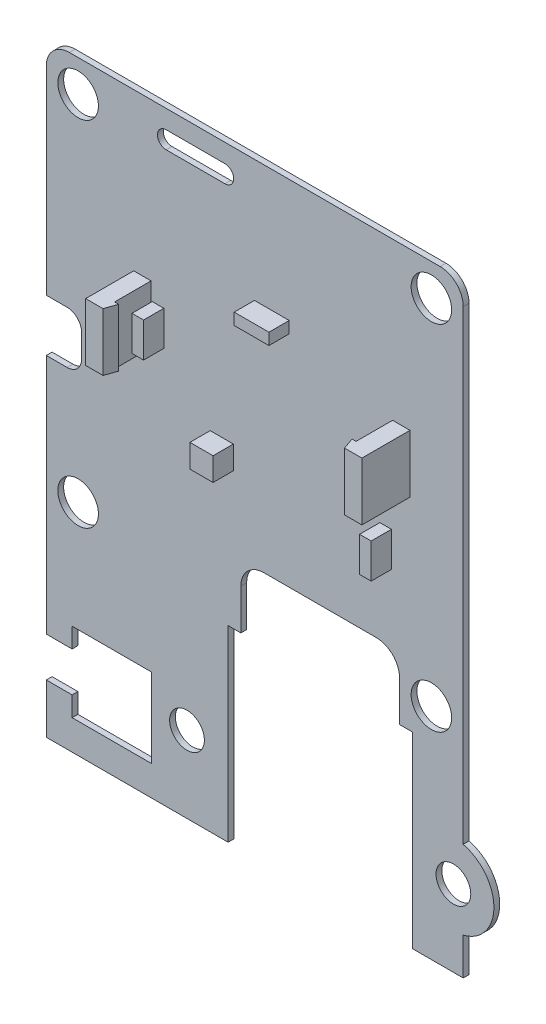
SolidWorks part; units mm, degrees
ref_plane "Front Plane" through (0, 0, 0) normal (0, 0, 1) x (1, 0, 0)
ref_plane "Top Plane" through (0, 0, 0) normal (0, 1, 0) x (1, 0, 0)
ref_plane "Right Plane" through (0, 0, 0) normal (1, 0, 0) x (0, 0, -1)
sketch "Sketch1" plane through (0, 0, 0) normal (0, 0, 1) x (1, 0, 0)
  line L1 (-14.95, -2.4) -> (-14.95, -4.4) construction
  line L2 (-16.2, -1.15) -> (-16.2, -5.65)
  line L3 (-14.95, -2.4) -> (-14.95, -4.4)
  line L4 (-7.65, 14.9) -> (-2.57, 14.9) construction
  line L5 (13.6, -18.1) -> (13.6, -34.2)
  line L6 (13.6, -34.2) -> (18, -34.2)
  line L7 (-2.3, -34.2) -> (-2.3, -18.1)
  line L8 (16, 18) -> (-16, 18)
  line L9 (-18, 16) -> (-18, -1.15)
  line L10 (-18, -18) -> (-1.2, -18)
  line L11 (-1.2, -18) -> (-1.2, -14.5)
  line L12 (0.8, -12.5) -> (10.5, -12.5)
  line L13 (12.5, -14.5) -> (12.5, -18)
  line L14 (12.5, -18) -> (18, -18)
  line L15 (18, -18) -> (18, 16)
  line L16 (16, 18) -> (-16, 18)
  line L17 (-18, 16) -> (-18, -1.15)
  line L18 (-18, -18) -> (-1.2, -18)
  line L19 (-1.2, -18) -> (-1.2, -14.5)
  line L20 (0.8, -12.5) -> (10.5, -12.5)
  line L21 (12.5, -14.5) -> (12.5, -18)
  line L22 (12.5, -18) -> (18, -18)
  line L23 (18, -18) -> (18, 16)
  line L24 (-2.3, -18.1) -> (-18, -18.1)
  line L25 (-18, -18.1) -> (-18, -26.4854)
  line L29 (-18, -34.2) -> (-2.3, -34.2)
  line L30 (-2.3, -34.2) -> (-2.3, -18.1)
  line L31 (-2.3, -18.1) -> (-18, -18.1)
  line L32 (-18, -18.1) -> (-18, -26.4854)
  line L36 (-18, -34.2) -> (-2.3, -34.2)
  line L37 (18, -34.2) -> (18, -30.9952)
  line L38 (18, -24.2048) -> (18, -18.1)
  line L39 (18, -18.1) -> (13.6, -18.1)
  line L40 (13.6, -18.1) -> (13.6, -34.2)
  line L41 (13.6, -34.2) -> (18, -34.2)
  line L42 (18, -34.2) -> (18, -30.9952)
  line L43 (18, -24.2048) -> (18, -18.1)
  line L44 (18, -18.1) -> (13.6, -18.1)
  line L45 (-7.65, 16.4) -> (-2.57, 16.4) construction
  line L46 (-7.65, 14.9) -> (-2.57, 14.9)
  line L47 (-7.65, 16.4) -> (-2.57, 16.4)
  line L48 (-18, -1.15) -> (-18, -18.1)
  line L49 (18, -18) -> (18, -18.1)
  line L50 (13.6, -18.1) -> (13.6, -18)
  line L51 (-2.3, -18.1) -> (-2.3, -18)
  line L112 (-18, -1.15) -> (-16.2, -1.15)
  line L113 (-18, -1.15) -> (-16.2, -1.15)
  line L114 (-14.95, -2.4) -> (-14.95, -4.4)
  line L115 (-14.95, -2.4) -> (-14.95, -4.4)
  line L116 (-16.2, -5.65) -> (-18, -5.65)
  line L117 (-16.2, -5.65) -> (-18, -5.65)
  line L118 (-18, -5.65) -> (-18, -18)
  line L119 (-18, -5.65) -> (-18, -18)
  line L153 (-18, -26.4854) -> (-15.77, -26.4854)
  line L154 (-18, -26.4854) -> (-15.77, -26.4854)
  line L155 (-15.77, -26.4854) -> (-15.77, -24.78)
  line L156 (-15.77, -26.4854) -> (-15.77, -24.78)
  line L157 (-15.77, -24.78) -> (-8.93, -24.78)
  line L158 (-15.77, -24.78) -> (-8.93, -24.78)
  line L186 (-15.77, -29.9146) -> (-18, -29.9146)
  line L187 (-15.77, -29.9146) -> (-18, -29.9146)
  line L234 (-8.93, -24.78) -> (-8.93, -31.62)
  line L235 (-8.93, -24.78) -> (-8.93, -31.62)
  line L236 (-8.93, -31.62) -> (-15.77, -31.62)
  line L237 (-8.93, -31.62) -> (-15.77, -31.62)
  line L238 (-15.77, -31.62) -> (-15.77, -29.9146)
  line L239 (-15.77, -31.62) -> (-15.77, -29.9146)
  line L240 (-18, -29.9146) -> (-18, -34.2)
  line L241 (-18, -29.9146) -> (-18, -34.2)
  arc A0 (-16.2, -5.65) -> (-14.95, -4.4) centre (-16.2, -4.4) ccw construction
  arc A3 (18, -30.9952) -> (18, -24.2048) centre (17.15, -27.6) ccw
  arc A4 (-16, 18) -> (-18, 16) centre (-16, 16) ccw
  arc A5 (0.8, -12.5) -> (-1.2, -14.5) centre (0.8, -14.5) ccw
  arc A6 (12.5, -14.5) -> (10.5, -12.5) centre (10.5, -14.5) ccw
  arc A7 (18, 16) -> (16, 18) centre (16, 16) ccw
  arc A8 (-16, 18) -> (-18, 16) centre (-16, 16) ccw
  arc A9 (0.8, -12.5) -> (-1.2, -14.5) centre (0.8, -14.5) ccw
  arc A10 (12.5, -14.5) -> (10.5, -12.5) centre (10.5, -14.5) ccw
  arc A11 (18, 16) -> (16, 18) centre (16, 16) ccw
  arc A12 (18, -30.9952) -> (18, -24.2048) centre (17.15, -27.6) ccw
  arc A13 (-14.95, -2.4) -> (-16.2, -1.15) centre (-16.2, -2.4) ccw construction
  arc A14 (-16.2, -5.65) -> (-14.95, -4.4) centre (-16.2, -4.4) ccw
  arc A15 (-14.95, -2.4) -> (-16.2, -1.15) centre (-16.2, -2.4) ccw
  circle A18 centre (17.15, -27.6) radius 1.5 construction
  circle A19 centre (-5.85, -27.6) radius 1.5 construction
  circle A22 centre (15.25, 15.25) radius 1.75
  circle A23 centre (15.25, -15.25) radius 1.75
  circle A24 centre (17.15, -27.6) radius 1.5
  circle A25 centre (-5.85, -27.6) radius 1.5
  circle A26 centre (-15.25, -15.25) radius 1.75
  circle A27 centre (-15.25, 15.25) radius 1.75
  arc A28 (-2.57, 14.9) -> (-2.57, 16.4) centre (-2.57, 15.65) ccw construction
  arc A29 (-7.65, 16.4) -> (-7.65, 14.9) centre (-7.65, 15.65) ccw construction
  arc A30 (-2.57, 14.9) -> (-2.57, 16.4) centre (-2.57, 15.65) ccw
  arc A31 (-7.65, 16.4) -> (-7.65, 14.9) centre (-7.65, 15.65) ccw
  circle A46 centre (15.25, -15.25) radius 1.75 construction
  circle A47 centre (-15.25, -15.25) radius 1.75 construction
  circle A48 centre (-15.25, 15.25) radius 1.75 construction
  circle A49 centre (15.25, 15.25) radius 1.75 construction
  arc A62 (-14.95, -2.4) -> (-16.2, -1.15) centre (-16.2, -2.4) ccw
  arc A63 (-14.95, -2.4) -> (-16.2, -1.15) centre (-16.2, -2.4) ccw
  arc A64 (-16.2, -5.65) -> (-14.95, -4.4) centre (-16.2, -4.4) ccw
  arc A65 (-16.2, -5.65) -> (-14.95, -4.4) centre (-16.2, -4.4) ccw
  dimension "D1" = 0
  dimension "D2" = 0
  dimension "D3" = 0
extrude "Base shape" add sketch "Sketch1" along normal blind 0.5 contours L23 A11 L16 A8 L17 L18 L19 A9 L20 A10 L21 L22 A31 L47 A30 L46 A27 A26 A23 A22 A15 L3 A14 L2 | L31 L51 L18 L48 | L36 L30 L31 L32 A25 | L50 L44 L49 L22 | L42 A12 L43 L44 L40 L41 A24 region at (-0.1312, 0.8573, 0) region at (-10.15, -18.05, 0) region at (-10.15, -18.3249, 0) region at (15.8, -18.05, 0) region at (16.2483, -26.2681, 0)
sketch "Sketch2" plane through (0, 0, 0.5) normal (0, 0, 1) x (1, 0, 0)
  line L0 (1.475, 16.95) -> (1.475, -13.05) construction
  line L1 (-7.85, 1.45) -> (-8.85, 1.45) construction
  line L2 (-0.025, 7.45) -> (2.975, 7.45)
  line L3 (-0.025, 7.45) -> (-0.025, 6.45)
  line L4 (11.8, 16.95) -> (-8.85, 16.95)
  line L5 (-8.85, 16.95) -> (-8.85, -13.05)
  line L6 (-8.85, -13.05) -> (11.8, -13.05)
  line L7 (11.8, -13.05) -> (11.8, 16.95)
  line L8 (11.8, 16.95) -> (-8.85, 16.95)
  line L9 (-8.85, 16.95) -> (-8.85, -13.05)
  line L10 (-8.85, -13.05) -> (11.8, -13.05)
  line L11 (11.8, -13.05) -> (11.8, 16.95)
  line L12 (-0.025, 6.45) -> (2.975, 6.45)
  line L13 (2.975, 7.45) -> (2.975, 6.45)
  line L14 (-0.025, 7.45) -> (2.975, 6.45) construction
  line L15 (-0.025, 6.45) -> (2.975, 7.45) construction
  line L16 (-8.85, 2.95) -> (-7.85, 2.95)
  line L17 (-8.85, 2.95) -> (-8.85, -0.05)
  line L18 (-8.85, -0.05) -> (-7.85, -0.05)
  line L19 (-7.85, 2.95) -> (-7.85, -0.05)
  line L20 (-3.85, -4.2) -> (-1.85, -4.2)
  line L21 (-3.85, -4.2) -> (-3.85, -6.2)
  line L22 (-3.85, -6.2) -> (-1.85, -6.2)
  line L23 (-1.85, -4.2) -> (-1.85, -6.2)
  line L24 (11.8, -3.75) -> (10.8, -3.75)
  line L25 (11.8, -3.75) -> (11.8, -6.75)
  line L26 (11.8, -6.75) -> (10.8, -6.75)
  line L27 (10.8, -3.75) -> (10.8, -6.75)
  line L28 (11.8, 1.95) -> (10.8, 1.95)
  line L29 (11.8, 1.95) -> (11.8, -1.05)
  line L30 (11.8, -1.05) -> (10.8, -1.05)
  line L31 (10.8, 1.95) -> (10.8, -1.05)
  line L32 (-3.85, -5.2) -> (-1.85, -5.2) construction
  line L33 (-2.85, -4.2) -> (-2.85, -6.2) construction
  line L34 (10.8, 0.45) -> (11.8, 0.45) construction
  line L35 (10.8, -5.25) -> (11.8, -5.25) construction
  point P6 (1.475, 6.95)
  dimension "D2" = 3
  dimension "D3" = 1
  dimension "D4" = 10
  dimension "D5" = 7.8
  dimension "D6" = 16.5
  dimension "D7" = 7.85
  dimension "D8" = 6
  dimension "D9" = 2
  dimension "D10" = 15.5
  dimension "D1" = 0
extrude "RX supports" add sketch "Sketch2" along normal blind 1.75 contours L13 L2 L3 L12 | L19 L16 L9 L18 | L23 L20 L21 L22 | L28 L31 L30 L11 | L24 L27 L26 L11 region at (1.475, 6.95, 0.5) region at (11.3, 0.45, 0.5) region at (-8.35, 1.45, 0.5) region at (11.3, -5.25, 0.5) region at (-2.85, -5.2, 0.5)
sketch "Sketch3" plane through (0, 0, 0.5) normal (0, 0, 1) x (1, 0, 0)
  line L0 (-8.85, 1.95) -> (11.8, 1.95) construction
  line L1 (1.475, 16.95) -> (1.475, -13.05) construction
  line L2 (-8.95, 4.45) -> (-10.45, 4.45)
  line L3 (-8.95, 4.45) -> (-8.95, -0.55)
  line L4 (11.8, 16.95) -> (-8.85, 16.95)
  line L5 (-8.85, 16.95) -> (-8.85, -13.05)
  line L6 (-8.85, -13.05) -> (11.8, -13.05)
  line L7 (11.8, -13.05) -> (11.8, 16.95)
  line L8 (11.8, 16.95) -> (-8.85, 16.95)
  line L9 (-8.85, 16.95) -> (-8.85, -13.05)
  line L10 (-8.85, -13.05) -> (11.8, -13.05)
  line L11 (11.8, -13.05) -> (11.8, 16.95)
  line L12 (-8.95, -0.55) -> (-10.45, -0.55)
  line L13 (-10.45, 4.45) -> (-10.45, -0.55)
  line L14 (11.9, -0.55) -> (13.4, -0.55)
  line L15 (13.4, 4.45) -> (13.4, -0.55)
  line L16 (11.9, 4.45) -> (13.4, 4.45)
  line L17 (11.9, 4.45) -> (11.9, -0.55)
  point P10 (-10.45, 1.95)
  dimension "D2" = 5
  dimension "D3" = 1.5
  dimension "D4" = 0.1
  dimension "D1" = 0
extrude "Clip base" add sketch "Sketch3" along normal offset from surface (3.15 mm away) 0.2 contours L2 L13 L12 L3 | L16 L17 L14 L15 region at (-9.7, 1.95, 0.5) region at (12.65, 1.95, 0.5) offset beyond the face yes
sketch "Sketch4" plane through (0, 0, 3.65) normal (0, 0, 1) x (1, 0, 0)
  line L0 (-8.95, -0.55) -> (-10.45, -0.55) construction
  line L1 (-10.45, 4.45) -> (-8.6, 4.45)
  line L2 (-10.45, 4.45) -> (-10.45, -0.55)
  line L3 (-10.45, -0.55) -> (-8.6, -0.55)
  line L4 (-8.6, 4.45) -> (-8.6, -0.55)
  line L5 (-8.95, 4.45) -> (-8.95, -0.55) construction
  line L6 (-10.45, 1.95) -> (13.4, 1.95) construction
  line L7 (13.4, 4.45) -> (13.4, -0.55) construction
  line L8 (1.475, 4.45) -> (1.475, -0.55) construction
  line L9 (11.55, 4.45) -> (11.55, -0.55)
  line L10 (13.4, 4.45) -> (11.55, 4.45)
  line L11 (13.4, 4.45) -> (13.4, -0.55)
  line L12 (13.4, -0.55) -> (11.55, -0.55)
  point P17 (1.475, 1.95)
  dimension "D1" = 0.35
extrude "Clip top" add sketch "Sketch4" along normal blind 1
sketch "Sketch5" plane through (0, -0.55, 0) normal (0, -1, 0) x (1, 0, 0)
  line L0 (-8.6, 3.65) -> (-8.95, 4.65)
  line L1 (-10.45, 4.65) -> (-8.6, 4.65) construction
  line L2 (-8.95, 4.65) -> (-8.6, 4.65)
  line L3 (-8.6, 4.65) -> (-8.6, 3.65)
  line L4 (-8.95, 3.65) -> (-8.95, 0.5) construction
  line L5 (11.55, 3.65) -> (11.9, 4.65)
  line L6 (11.55, 4.65) -> (13.4, 4.65) construction
  line L7 (11.9, 4.65) -> (11.55, 4.65)
  line L8 (11.55, 4.65) -> (11.55, 3.65)
  line L9 (11.9, 3.65) -> (11.9, 0.5) construction
extrude "Clip chamfer" cut sketch "Sketch5" against normal up to next
